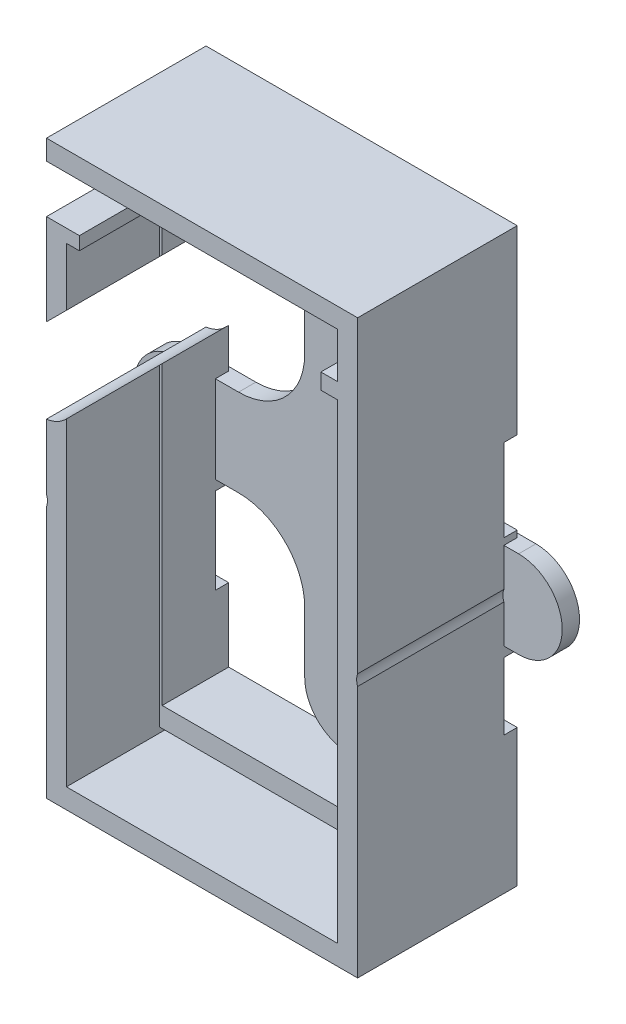
SolidWorks part; units mm, degrees
note: The reader was unsure of these and kept them because the rebuilt part matched: shared geometry of "Sketch4<3>", "Sketch6<4>", "Sketch6<3>", "Sketch4<4>".
ref_plane "Front Plane" through (0, 0, 0) normal (0, 0, 1) x (1, 0, 0)
ref_plane "Top Plane" through (0, 0, 0) normal (0, 1, 0) x (1, 0, 0)
ref_plane "Right Plane" through (0, 0, 0) normal (1, 0, 0) x (0, 0, -1)
sketch "Sketch2" plane through (0, 0, 0) normal (1, 0, 0) x (0, 0, -1)
  line L0 (0, 12.5857) -> (0, 0)
  line L1 (0, -12.5857) -> (4.4704, -13.9065)
  line L2 (4.4704, 13.9065) -> (4.4704, 16.4465)
  line L3 (4.4704, 16.4465) -> (0, 16.4465)
  line L4 (0, 16.4465) -> (0, 44.45)
  line L5 (0, 44.45) -> (59.7512, 44.45)
  line L6 (59.7512, 44.45) -> (59.7512, 39.37)
  line L7 (59.7512, 39.37) -> (64.8312, 39.37)
  line L8 (64.8312, 39.37) -> (64.8312, 49.53)
  line L9 (64.8312, 49.53) -> (-5.08, 49.53)
  line L10 (-5.08, 49.53) -> (-5.08, 0)
  line L12 (0, 0) -> (-5.08, 0)
  line L17 (0, 12.0425) -> (0, 12.5857) construction
  line L19 (4.4704, 13.9065) -> (0, 12.5857)
  line L20 (4.4704, 13.9065) -> (0, 12.5857)
  line L21 (0, -12.5857) -> (4.4704, -13.9065)
  dimension "D1" = 2.54
  dimension "D2" = 5.08
  dimension "D3" = 44.45
  dimension "D4" = 5.08
  dimension "D5" = 5.08
  dimension "D6" = 5.08
revolve "Body" add sketch "Sketch2" angle 360 about L12
sketch "Sketch4" plane through (0, 0, 0) normal (0, 0, 1) x (1, 0, 0)
  line L0 (-3.6576, 12.0425) -> (-3.6576, 10.4835)
  line L1 (-3.6576, 16.265) -> (-3.6576, 12.0425)
  line L2 (-3.6576, 16.265) -> (-3.6576, 12.0425) construction
  line L3 (-3.6576, 12.0425) -> (-3.6576, 10.4835) construction
  line L4 (3.6576, 12.0425) -> (3.6576, 10.4835)
  line L5 (3.6576, 16.265) -> (3.6576, 12.0425)
  line L6 (3.6576, 16.265) -> (3.6576, 12.0425) construction
  line L7 (3.6576, 12.0425) -> (3.6576, 10.4835) construction
  line L8 (12.0425, 3.6576) -> (10.4835, 3.6576)
  line L9 (16.265, 3.6576) -> (12.0425, 3.6576)
  line L10 (16.265, 3.6576) -> (12.0425, 3.6576) construction
  line L11 (12.0425, 3.6576) -> (10.4835, 3.6576) construction
  line L12 (12.0425, -3.6576) -> (10.4835, -3.6576)
  line L13 (16.265, -3.6576) -> (12.0425, -3.6576)
  line L14 (16.265, -3.6576) -> (12.0425, -3.6576) construction
  line L15 (12.0425, -3.6576) -> (10.4835, -3.6576) construction
  line L16 (3.6576, -12.0425) -> (3.6576, -10.4835)
  line L17 (3.6576, -16.265) -> (3.6576, -12.0425)
  line L18 (3.6576, -16.265) -> (3.6576, -12.0425) construction
  line L19 (3.6576, -12.0425) -> (3.6576, -10.4835) construction
  line L20 (-3.6576, -12.0425) -> (-3.6576, -10.4835)
  line L21 (-3.6576, -16.265) -> (-3.6576, -12.0425)
  line L22 (-3.6576, -16.265) -> (-3.6576, -12.0425) construction
  line L23 (-3.6576, -12.0425) -> (-3.6576, -10.4835) construction
  line L24 (-12.0425, 3.6576) -> (-10.4835, 3.6576)
  line L25 (-16.265, 3.6576) -> (-12.0425, 3.6576)
  line L26 (-16.265, 3.6576) -> (-12.0425, 3.6576) construction
  line L27 (-12.0425, 3.6576) -> (-10.4835, 3.6576) construction
  line L28 (-4.1656, -12.0425) -> (-4.1656, -10.4835)
  line L29 (-4.1656, -16.265) -> (-4.1656, -12.0425)
  line L30 (4.1656, -16.265) -> (4.1656, -12.0425)
  line L31 (4.1656, -12.0425) -> (4.1656, -10.4835)
  line L32 (12.0425, -4.1656) -> (10.4835, -4.1656)
  line L33 (16.265, -4.1656) -> (12.0425, -4.1656)
  line L34 (16.265, 4.1656) -> (12.0425, 4.1656)
  line L35 (12.0425, 4.1656) -> (10.4835, 4.1656)
  line L36 (4.1656, 12.0425) -> (4.1656, 10.4835)
  line L37 (4.1656, 16.265) -> (4.1656, 12.0425)
  line L38 (-4.1656, 16.265) -> (-4.1656, 12.0425)
  line L39 (-4.1656, 12.0425) -> (-4.1656, 10.4835)
  line L40 (-12.0425, 4.1656) -> (-10.4835, 4.1656)
  line L41 (-16.265, 4.1656) -> (-12.0425, 4.1656)
  line L42 (-10.4835, -4.1656) -> (-16.265, -4.1656)
  line L43 (-9.8783, 15.2664) -> (-15.2664, 9.8783) construction
  line L44 (-7.6332, 13.0214) -> (-13.0214, 7.6332)
  line L45 (-12.1233, 17.5115) -> (-17.5115, 12.1233)
  line L46 (0, 0) -> (-26.7135, 26.7135) construction
  line L47 (0, 0) -> (0, 36.3192) construction
  line L48 (-8.2611, -8.2611) -> (8.2611, 8.2611) construction
  line L49 (0, 0) -> (8.2611, -8.2611) construction
  arc A0 (-10.4835, 3.6576) -> (-3.6576, 10.4835) centre (-10.4835, 10.4835) ccw
  arc A1 (-10.4835, 3.6576) -> (-3.6576, 10.4835) centre (-10.4835, 10.4835) ccw construction
  arc A2 (3.6576, 16.265) -> (-3.6576, 16.265) centre (0, 16.265) ccw
  arc A3 (3.6576, 16.265) -> (-3.6576, 16.265) centre (0, 16.265) ccw construction
  arc A4 (3.6576, 10.4835) -> (10.4835, 3.6576) centre (10.4835, 10.4835) ccw
  arc A5 (3.6576, 10.4835) -> (10.4835, 3.6576) centre (10.4835, 10.4835) ccw construction
  arc A6 (16.265, -3.6576) -> (16.265, 3.6576) centre (16.265, 0) ccw
  arc A7 (16.265, -3.6576) -> (16.265, 3.6576) centre (16.265, 0) ccw construction
  arc A8 (10.4835, -3.6576) -> (3.6576, -10.4835) centre (10.4835, -10.4835) ccw
  arc A9 (10.4835, -3.6576) -> (3.6576, -10.4835) centre (10.4835, -10.4835) ccw construction
  arc A10 (-3.6576, -16.265) -> (3.6576, -16.265) centre (0, -16.265) ccw
  arc A11 (-3.6576, -16.265) -> (3.6576, -16.265) centre (0, -16.265) ccw construction
  arc A12 (-3.6576, -10.4835) -> (-10.4835, -3.6576) centre (-10.4835, -10.4835) ccw
  arc A13 (-3.6576, -10.4835) -> (-10.4835, -3.6576) centre (-10.4835, -10.4835) ccw construction
  arc A14 (-16.265, 3.6576) -> (-16.265, -3.6576) centre (-16.265, 0) ccw
  arc A15 (-16.265, 3.6576) -> (-16.265, -3.6576) centre (-16.265, 0) ccw construction
  arc A16 (-4.1656, -10.4835) -> (-10.4835, -4.1656) centre (-10.4835, -10.4835) ccw
  arc A17 (-4.1656, -16.265) -> (4.1656, -16.265) centre (0, -16.265) ccw
  arc A18 (10.4835, -4.1656) -> (4.1656, -10.4835) centre (10.4835, -10.4835) ccw
  arc A19 (16.265, -4.1656) -> (16.265, 4.1656) centre (16.265, 0) ccw
  arc A20 (4.1656, 10.4835) -> (10.4835, 4.1656) centre (10.4835, 10.4835) ccw
  arc A21 (4.1656, 16.265) -> (-4.1656, 16.265) centre (0, 16.265) ccw
  arc A22 (-10.4835, 4.1656) -> (-4.1656, 10.4835) centre (-10.4835, 10.4835) ccw
  arc A23 (-16.265, 4.1656) -> (-16.265, -4.1656) centre (-16.265, 0) ccw
  circle A24 centre (16.265, 0) radius 1.5
  circle A25 centre (0, 16.265) radius 1.5
  circle A26 centre (-16.265, 0) radius 1.5
  circle A27 centre (0, -16.265) radius 1.5
  arc A28 (-7.6332, 13.0214) -> (-12.1233, 17.5115) centre (-9.8783, 15.2664) ccw
  arc A29 (-17.5115, 12.1233) -> (-13.0214, 7.6332) centre (-15.2664, 9.8783) ccw
  circle A30 centre (8.2611, 8.2611) radius 3.175
  circle A31 centre (8.2611, -8.2611) radius 3.175
  circle A32 centre (-8.2611, -8.2611) radius 3.175
  circle A33 centre (-8.2611, 8.2611) radius 3.175
  point P68 (-12.5724, 12.5724)
  dimension "D2" = 3
  dimension "D7" = 6.35
  dimension "D3" = 45
  dimension "D4" = 17.78
  dimension "D5" = 6.35
  dimension "D6" = 7.62
  dimension "D1" = 0.508
extrude "X-Wing" cut sketch "Sketch4" against normal blind 12.7 contours A17 L30 L31 A18 L32 L33 A19 L34 L35 A20 L36 L37 A21 L38 L39 A22 L40 L41 A23 L42 A16 L28 L29
extrude "Holes" cut sketch "Sketch4<3>" along normal blind 9.525 contours A27 | A26 | A24 | A25 | A28 L45 A29 L44 | A33 | A30 | A31 | A32
sketch "Sketch4<3>" plane through (0, 0, 0) normal (0, 0, 1) x (1, 0, 0) same geometry as "Sketch4"
sketch "Sketch6" plane through (0, 0, 5.08) normal (0, 0, 1) x (1, 0, 0)
  line L0 (-14.605, 22.225) -> (14.605, 22.225)
  line L1 (-12.954, 28.067) -> (12.954, 28.067)
  line L2 (-12.954, 28.067) -> (-12.954, -22.733)
  line L3 (-12.954, -22.733) -> (12.954, -22.733)
  line L4 (12.954, 28.067) -> (12.954, -22.733)
  line L5 (-12.954, 28.067) -> (12.954, -22.733) construction
  line L6 (-12.954, -22.733) -> (12.954, 28.067) construction
  line L7 (-12.7, 20.32) -> (12.7, 20.32)
  line L8 (-12.7, 20.32) -> (-12.7, -20.32)
  line L9 (-12.7, -20.32) -> (12.7, -20.32)
  line L10 (12.7, 20.32) -> (12.7, -20.32)
  line L11 (-12.7, 20.32) -> (12.7, -20.32) construction
  line L12 (-12.7, -20.32) -> (12.7, 20.32) construction
  line L13 (14.605, 22.225) -> (14.605, -22.225)
  line L14 (-14.605, -22.225) -> (14.605, -22.225)
  line L15 (-14.605, 22.225) -> (-14.605, -22.225)
  line L16 (-14.859, 29.972) -> (-14.859, -24.638)
  line L17 (-14.859, -24.638) -> (14.859, -24.638)
  line L18 (14.859, 29.972) -> (14.859, -24.638)
  line L19 (-14.859, 29.972) -> (14.859, 29.972)
  line L20 (-14.859, 23.4798) -> (-11.7157, 23.4798)
  line L21 (-12.954, 28.067) -> (-14.859, 28.067)
  line L22 (-11.7157, 23.4798) -> (-11.7157, 22.225)
  line L23 (-12.954, -22.733) -> (12.954, -22.733)
  line L24 (-12.954, -22.733) -> (-12.954, 22.733)
  line L25 (-12.954, 22.733) -> (12.954, 22.733) construction
  line L26 (12.954, -22.733) -> (12.954, 22.733)
  line L27 (-12.954, -22.733) -> (12.954, 22.733) construction
  line L28 (-12.954, 22.733) -> (12.954, -22.733) construction
  line L30 (12.954, 23.7342) -> (11.35, 23.7342)
  line L31 (12.954, 23.7342) -> (12.954, 22.225)
  line L32 (12.954, 22.225) -> (11.35, 22.225)
  line L33 (11.35, 23.7342) -> (11.35, 22.225)
  line L34 (12.954, 23.7342) -> (11.35, 22.225) construction
  line L35 (12.954, 22.225) -> (11.35, 23.7342) construction
  circle A0 centre (-9.906, 36.322) radius 1.27
  circle A1 centre (-23.749, -23.368) radius 1.27
  circle A2 centre (23.114, -15.748) radius 1.27
  circle A3 centre (18.034, 36.322) radius 1.27
  circle A4 centre (18.034, 36.322) radius 1.5875 construction
  circle A5 centre (-9.906, 36.322) radius 1.5875 construction
  circle A6 centre (-23.749, -23.368) radius 1.5 construction
  circle A7 centre (23.114, -15.748) radius 1.5875 construction
  point P4 (0, 0)
  point P9 (0, 0)
  point P12 (0, 2.667)
  point P41 (0, 0)
  point P48 (12.152, 22.9796)
  circle M35 centre (16.265, 0) radius 1.5
  circle M36 centre (-16.265, 0) radius 1.5
  arc M45 (-13.0214, 7.6332) -> (-17.5115, 12.1233) centre (-15.2664, 9.8783) cw
  line M46 (-17.5115, 12.1233) -> (-12.1233, 17.5115)
  line M49 (-11.2055, 9.4491) -> (-13.0214, 7.6332)
  dimension "D9" = 2.54
  dimension "D1" = 25.908
  dimension "D2" = 50.8
  dimension "D3" = 45.466
  dimension "D5" = 40.64
  dimension "D6" = 25.4
  dimension "D10" = 1.905
extrude "Chip" add sketch "Sketch6" along normal blind 6.35 contours L2 L14 L4 L0 L8 L7 L10 L9 M46 M49 M45 | L16 L17 L18 L19
extrude "9V" add sketch "Sketch6<4>" along normal blind 15.24 contours L19 L16 L15 L0 L2 L1 L4 L13 L14 L3 L17 L18 M46 M45 M36 M35 | L15 L14 L2 M45 | L4 L14 L13 L0 | L0 L15 L2 M46 | L20 L16 L15 L0 L2 M46 | L22 L20 L2 L0 | L30 L33 L32 L31
sketch "Sketch6<4>" plane through (0, 0, 5.08) normal (0, 0, 1) x (1, 0, 0) same geometry as "Sketch6"
extrude "Air holes" cut sketch "Sketch6<3>" against normal blind 9.525 contours A1 | A2 | A0 | A3
sketch "Sketch6<3>" plane through (0, 0, 5.08) normal (0, 0, 1) x (1, 0, 0) same geometry as "Sketch6"
extrude "Lift" add sketch "Sketch4<4>" along normal blind 1.27 from vertex at 5.08 contours A16 L42 A23 L41 L40 A22 L39 L38 A21 L37 L36 A20 L35 L34 A19 L33 L32 A18 L31 L30 A17 L29 L28 starting at point (-12.7, -20.32, 5.08)
sketch "Sketch4<4>" plane through (0, 0, 0) normal (0, 0, 1) x (1, 0, 0) same geometry as "Sketch4"
sketch "Sketch7" plane through (0, 0, 5.08) normal (0, 0, 1) x (1, 0, 0)
  line L1 (11.766, 12.6721) -> (19.309, 12.6721)
  line L2 (11.766, 12.6721) -> (11.766, 4.7914)
  line L3 (11.766, 4.7914) -> (19.309, 4.7914)
  line L4 (19.309, 12.6721) -> (19.309, 4.7914)
  line L5 (11.766, 12.6721) -> (19.309, 4.7914) construction
  line L6 (11.766, 4.7914) -> (19.309, 12.6721) construction
  line L7 (11.766, -5.1158) -> (19.309, -5.1158)
  line L8 (11.766, -5.1158) -> (11.766, -11.5329)
  line L9 (11.766, -11.5329) -> (19.309, -11.5329)
  line L10 (19.309, -5.1158) -> (19.309, -11.5329)
  line L11 (11.766, -5.1158) -> (19.309, -11.5329) construction
  line L12 (11.766, -11.5329) -> (19.309, -5.1158) construction
  line L13 (-17.7303, -5.1158) -> (-11.9886, -5.1158)
  line L14 (-17.7303, -5.1158) -> (-17.7303, -13.3342)
  line L15 (-17.7303, -13.3342) -> (-11.9886, -13.3342)
  line L16 (-11.9886, -5.1158) -> (-11.9886, -13.3342)
  line L17 (-17.7303, -5.1158) -> (-11.9886, -13.3342) construction
  line L18 (-17.7303, -13.3342) -> (-11.9886, -5.1158) construction
  point P4 (15.5375, 8.7317)
  point P9 (15.5375, -8.3243)
  point P14 (-14.8595, -9.225)
extrude "Air Slots" cut sketch "Sketch7" along normal blind 1.27
sketch "Sketch8" plane through (0, 0, 5.08) normal (0, 0, 1) x (1, 0, 0)
  line L0 (0, 0) -> (0, 28.448) construction
  line L1 (-11.684, -22.352) -> (11.684, -22.352)
  line L2 (-12.954, -21.082) -> (-12.954, 21.082)
  line L3 (-11.684, 22.352) -> (-10.795, 22.352)
  line L4 (12.954, -21.082) -> (12.954, 21.082)
  line L5 (-12.954, -22.352) -> (12.954, 22.352) construction
  line L6 (-12.954, 22.352) -> (12.954, -22.352) construction
  line L7 (-15.494, -21.082) -> (-15.494, -4.7901)
  line L8 (-9.525, 28.448) -> (9.525, 28.448)
  line L9 (-13.335, 24.5157) -> (-13.335, 27.178)
  line L10 (-10.795, 22.352) -> (-10.795, 27.178)
  line L11 (10.795, 22.352) -> (11.684, 22.352)
  line L12 (10.795, 22.352) -> (10.795, 27.178)
  line L13 (-9.525, 30.988) -> (9.525, 30.988)
  line L14 (13.335, 24.5157) -> (13.335, 27.178)
  line L15 (15.494, -21.082) -> (15.494, 21.082)
  line L16 (-11.684, -24.892) -> (11.684, -24.892)
  line L17 (-15.494, -2.8851) -> (-15.494, 21.082)
  line L18 (-28.194, -2.8851) -> (-15.494, -2.8851)
  line L19 (-28.194, -2.8851) -> (-28.194, -4.7901)
  line L20 (-28.194, -4.7901) -> (-15.494, -4.7901)
  line L21 (-13.335, 27.178) -> (-10.795, 27.178)
  line L22 (-13.335, 24.5157) -> (-10.795, 24.5157)
  circle A0 centre (0, 1.27) radius 28.8925 construction
  arc A1 (-11.684, 22.352) -> (-12.954, 21.082) centre (-11.684, 21.082) ccw
  arc A2 (-9.525, 28.448) -> (-10.795, 27.178) centre (-9.525, 27.178) ccw
  arc A3 (9.525, 28.448) -> (10.795, 27.178) centre (9.525, 27.178) cw
  arc A4 (11.684, 22.352) -> (12.954, 21.082) centre (11.684, 21.082) cw
  arc A5 (12.954, -21.082) -> (11.684, -22.352) centre (11.684, -21.082) cw
  arc A6 (-11.684, -22.352) -> (-12.954, -21.082) centre (-11.684, -21.082) cw
  arc A7 (-13.335, 24.5157) -> (-15.494, 21.082) centre (-11.684, 21.082) ccw
  arc A8 (-9.525, 30.988) -> (-13.335, 27.178) centre (-9.525, 27.178) ccw
  arc A9 (9.525, 30.988) -> (13.335, 27.178) centre (9.525, 27.178) cw
  arc A10 (13.335, 24.5157) -> (15.494, 21.082) centre (11.684, 21.082) cw
  arc A11 (15.494, -21.082) -> (11.684, -24.892) centre (11.684, -21.082) cw
  arc A12 (-11.684, -24.892) -> (-15.494, -21.082) centre (-11.684, -21.082) cw
  point P0 (0, 0)
  dimension "D5" = 1.27
  dimension "D1" = 44.704
  dimension "D2" = 25.908
  dimension "D3" = 50.8
  dimension "D4" = 1.27
  dimension "D6" = 12.7
  dimension "D7" = 1.905
ref_plane "Plane1" through (0, 0, 5.08) normal (0, 0, 1) x (1, 0, 0)
other "SurfaceCut1"
sketch "Sketch9" plane through (0, 0, 5.08) normal (0, 0, -1) x (-1, 0, 0)
  line L0 (-0.9535, -20.32) -> (0.9535, -20.32)
  line L1 (-14.859, -4.1656) -> (-12.7, -4.1656)
  line L2 (-14.859, 4.1656) -> (-12.7, 4.1656)
  line L3 (-0.9535, 20.32) -> (0.9535, 20.32)
  line L4 (12.7, 4.1656) -> (14.859, 4.1656)
  line L5 (12.7, -4.1656) -> (14.859, -4.1656)
  line L50 (12.7, 20.32) -> (12.7, 16.9348)
  line L51 (12.7, 16.9348) -> (14.859, 14.7758)
  line L52 (14.859, 14.7758) -> (14.859, 23.4798)
  line L53 (14.859, 23.4798) -> (11.7157, 23.4798)
  line L54 (11.7157, 23.4798) -> (11.7157, 22.225)
  line L55 (11.7157, 22.225) -> (-11.35, 22.225)
  line L56 (-11.35, 22.225) -> (-11.35, 23.7342)
  line L57 (-11.35, 23.7342) -> (-12.954, 23.7342)
  line L58 (-12.954, 23.7342) -> (-12.954, 28.067)
  line L59 (-12.954, 28.067) -> (14.859, 28.067)
  line L60 (14.859, 28.067) -> (14.859, 29.972)
  line L61 (14.859, 29.972) -> (-14.859, 29.972)
  line L62 (-14.859, 29.972) -> (-14.859, 12.6721)
  line L63 (-14.859, 12.6721) -> (-12.7, 12.6721)
  line L64 (-12.7, 12.6721) -> (-12.7, 20.32)
  line L65 (-12.7, 20.32) -> (-0.9535, 20.32)
  line L66 (-4.1656, 16.265) -> (-4.1656, 10.4835)
  line L67 (-10.4835, 4.1656) -> (-12.7, 4.1656)
  line L68 (-12.7, 4.1656) -> (-12.7, 4.7914)
  line L69 (-12.7, 4.7914) -> (-14.859, 4.7914)
  line L70 (-14.859, 4.7914) -> (-14.859, 4.1656)
  line L71 (-14.859, 4.1656) -> (-16.265, 4.1656)
  line L72 (-16.265, -4.1656) -> (-14.859, -4.1656)
  line L73 (-14.859, -4.1656) -> (-14.859, -5.1158)
  line L74 (-14.859, -5.1158) -> (-12.7, -5.1158)
  line L75 (-12.7, -5.1158) -> (-12.7, -4.1656)
  line L76 (-12.7, -4.1656) -> (-10.4835, -4.1656)
  line L77 (-4.1656, -10.4835) -> (-4.1656, -16.265)
  line L78 (-0.9535, -20.32) -> (-12.7, -20.32)
  line L79 (-12.7, -20.32) -> (-12.7, -11.5329)
  line L80 (-12.7, -11.5329) -> (-14.859, -11.5329)
  line L81 (-14.859, -11.5329) -> (-14.859, -24.638)
  line L82 (-14.859, -24.638) -> (14.859, -24.638)
  line L83 (14.859, -24.638) -> (14.859, -13.3342)
  line L84 (14.859, -13.3342) -> (12.7, -13.3342)
  line L85 (12.7, -13.3342) -> (12.7, -20.32)
  line L86 (12.7, -20.32) -> (0.9535, -20.32)
  line L87 (4.1656, -16.265) -> (4.1656, -10.4835)
  line L88 (10.4835, -4.1656) -> (12.7, -4.1656)
  line L89 (12.7, -4.1656) -> (12.7, -5.1158)
  line L90 (12.7, -5.1158) -> (14.859, -5.1158)
  line L91 (14.859, -5.1158) -> (14.859, -4.1656)
  line L92 (14.859, -4.1656) -> (16.265, -4.1656)
  line L93 (16.265, 4.1656) -> (14.859, 4.1656)
  line L94 (14.859, 4.1656) -> (14.859, 6.7295)
  line L95 (13.0214, 7.6332) -> (12.7, 7.9546)
  line L96 (12.7, 7.9546) -> (12.7, 4.1656)
  line L97 (12.7, 4.1656) -> (10.4835, 4.1656)
  line L98 (4.1656, 10.4835) -> (4.1656, 16.265)
  line L99 (0.9535, 20.32) -> (12.7, 20.32)
  line L100 (12.7, 20.32) -> (12.7, 16.9348)
  line L101 (12.7, 16.9348) -> (14.859, 14.7758)
  line L102 (14.859, 14.7758) -> (14.859, 23.4798)
  line L103 (14.859, 23.4798) -> (11.7157, 23.4798)
  line L104 (11.7157, 23.4798) -> (11.7157, 22.225)
  line L105 (11.7157, 22.225) -> (-11.35, 22.225)
  line L106 (-11.35, 22.225) -> (-11.35, 23.7342)
  line L107 (-11.35, 23.7342) -> (-12.954, 23.7342)
  line L108 (-12.954, 23.7342) -> (-12.954, 28.067)
  line L109 (-12.954, 28.067) -> (14.859, 28.067)
  line L110 (14.859, 28.067) -> (14.859, 29.972)
  line L111 (14.859, 29.972) -> (-14.859, 29.972)
  line L112 (-14.859, 29.972) -> (-14.859, 12.6721)
  line L113 (-14.859, 12.6721) -> (-12.7, 12.6721)
  line L114 (-12.7, 12.6721) -> (-12.7, 20.32)
  line L115 (-12.7, 20.32) -> (-0.9535, 20.32)
  line L116 (-4.1656, 16.265) -> (-4.1656, 10.4835)
  line L117 (-10.4835, 4.1656) -> (-12.7, 4.1656)
  line L118 (-12.7, 4.1656) -> (-12.7, 4.7914)
  line L119 (-12.7, 4.7914) -> (-14.859, 4.7914)
  line L120 (-14.859, 4.7914) -> (-14.859, 4.1656)
  line L121 (-14.859, 4.1656) -> (-16.265, 4.1656)
  line L122 (-16.265, -4.1656) -> (-14.859, -4.1656)
  line L123 (-14.859, -4.1656) -> (-14.859, -5.1158)
  line L124 (-14.859, -5.1158) -> (-12.7, -5.1158)
  line L125 (-12.7, -5.1158) -> (-12.7, -4.1656)
  line L126 (-12.7, -4.1656) -> (-10.4835, -4.1656)
  line L127 (-4.1656, -10.4835) -> (-4.1656, -16.265)
  line L128 (-0.9535, -20.32) -> (-12.7, -20.32)
  line L129 (-12.7, -20.32) -> (-12.7, -11.5329)
  line L130 (-12.7, -11.5329) -> (-14.859, -11.5329)
  line L131 (-14.859, -11.5329) -> (-14.859, -24.638)
  line L132 (-14.859, -24.638) -> (14.859, -24.638)
  line L133 (14.859, -24.638) -> (14.859, -13.3342)
  line L134 (14.859, -13.3342) -> (12.7, -13.3342)
  line L135 (12.7, -13.3342) -> (12.7, -20.32)
  line L136 (12.7, -20.32) -> (0.9535, -20.32)
  line L137 (4.1656, -16.265) -> (4.1656, -10.4835)
  line L138 (10.4835, -4.1656) -> (12.7, -4.1656)
  line L139 (12.7, -4.1656) -> (12.7, -5.1158)
  line L140 (12.7, -5.1158) -> (14.859, -5.1158)
  line L141 (14.859, -5.1158) -> (14.859, -4.1656)
  line L142 (14.859, -4.1656) -> (16.265, -4.1656)
  line L143 (16.265, 4.1656) -> (14.859, 4.1656)
  line L144 (14.859, 4.1656) -> (14.859, 6.7295)
  line L145 (13.0214, 7.6332) -> (12.7, 7.9546)
  line L146 (12.7, 7.9546) -> (12.7, 4.1656)
  line L147 (12.7, 4.1656) -> (10.4835, 4.1656)
  line L148 (4.1656, 10.4835) -> (4.1656, 16.265)
  line L149 (0.9535, 20.32) -> (12.7, 20.32)
  arc A11 (-0.9535, 20.32) -> (-4.1656, 16.265) centre (0, 16.265) ccw
  arc A12 (-10.4835, 4.1656) -> (-4.1656, 10.4835) centre (-10.4835, 10.4835) ccw
  arc A13 (-16.265, 4.1656) -> (-16.265, -4.1656) centre (-16.265, 0) ccw
  arc A14 (-4.1656, -10.4835) -> (-10.4835, -4.1656) centre (-10.4835, -10.4835) ccw
  arc A15 (-4.1656, -16.265) -> (-0.9535, -20.32) centre (0, -16.265) ccw
  arc A16 (0.9535, -20.32) -> (4.1656, -16.265) centre (0, -16.265) ccw
  arc A17 (10.4835, -4.1656) -> (4.1656, -10.4835) centre (10.4835, -10.4835) ccw
  arc A18 (16.265, -4.1656) -> (16.265, 4.1656) centre (16.265, 0) ccw
  arc A19 (13.0214, 7.6332) -> (14.859, 6.7295) centre (15.2664, 9.8783) ccw
  arc A20 (4.1656, 10.4835) -> (10.4835, 4.1656) centre (10.4835, 10.4835) ccw
  arc A21 (4.1656, 16.265) -> (0.9535, 20.32) centre (0, 16.265) ccw
  arc A22 (-0.9535, 20.32) -> (-4.1656, 16.265) centre (0, 16.265) ccw
  arc A23 (-10.4835, 4.1656) -> (-4.1656, 10.4835) centre (-10.4835, 10.4835) ccw
  arc A24 (-16.265, 4.1656) -> (-16.265, -4.1656) centre (-16.265, 0) ccw
  arc A25 (-4.1656, -10.4835) -> (-10.4835, -4.1656) centre (-10.4835, -10.4835) ccw
  arc A26 (-4.1656, -16.265) -> (-0.9535, -20.32) centre (0, -16.265) ccw
  arc A27 (0.9535, -20.32) -> (4.1656, -16.265) centre (0, -16.265) ccw
  arc A28 (10.4835, -4.1656) -> (4.1656, -10.4835) centre (10.4835, -10.4835) ccw
  arc A29 (16.265, -4.1656) -> (16.265, 4.1656) centre (16.265, 0) ccw
  arc A30 (13.0214, 7.6332) -> (14.859, 6.7295) centre (15.2664, 9.8783) ccw
  arc A31 (4.1656, 10.4835) -> (10.4835, 4.1656) centre (10.4835, 10.4835) ccw
  arc A32 (4.1656, 16.265) -> (0.9535, 20.32) centre (0, 16.265) ccw
  dimension "D1" = 0
extrude "Boss-Extrude1" add sketch "Sketch9" along normal blind 0.381 contours L148 A32 L3 A22 L116 A23 L117 L2 L121 A24 L122 L1 L126 A25 L127 A26 L0 A27 L137 A28 L138 L5 L142 A29 L143 L4 L147 A31
